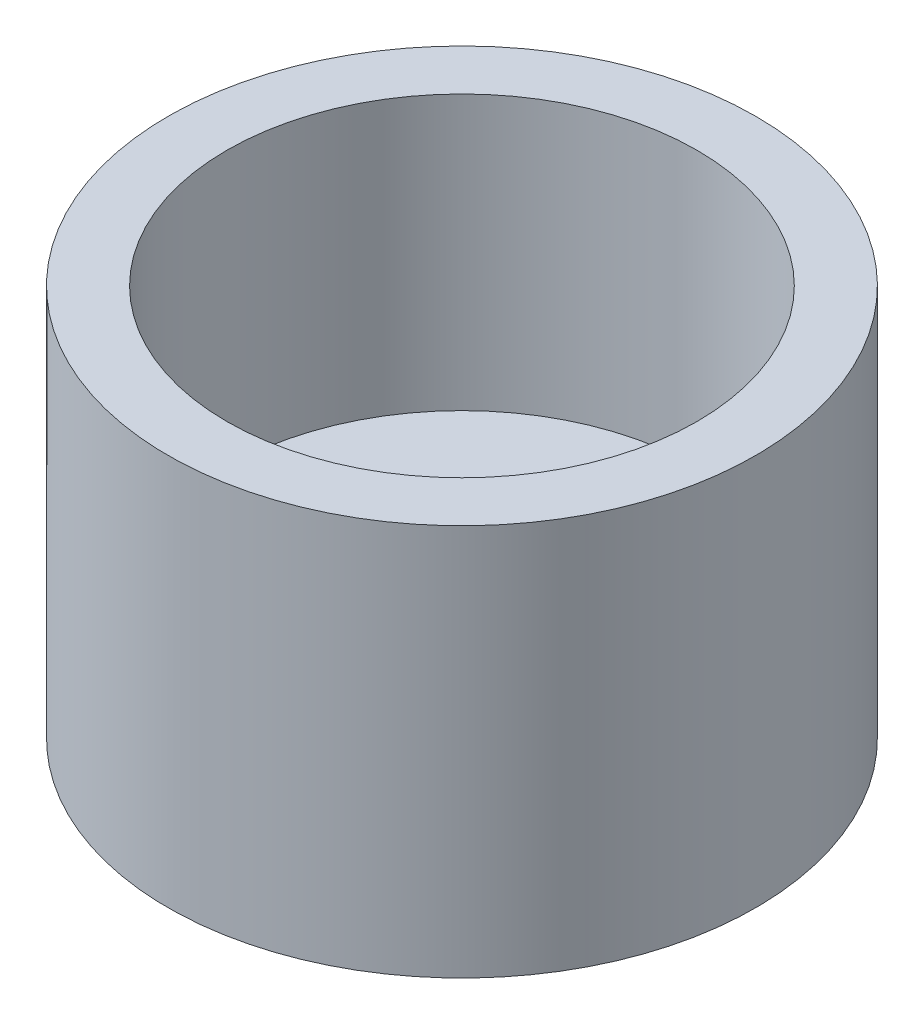
SolidWorks part; units mm, degrees
material "1.0035 (S185)"
ref_plane "Piano frontale" through (0, 0, 0) normal (0, 0, 1) x (1, 0, 0)
ref_plane "Piano superiore" through (0, 0, 0) normal (0, 1, 0) x (1, 0, 0)
ref_plane "Piano destro" through (0, 0, 0) normal (1, 0, 0) x (0, 0, -1)
sketch "Schizzo1" plane through (0, 0, 0) normal (0, 0, 1) x (1, 0, 0)
  line L0 (0, 0) -> (-15, 0)
  line L1 (-15, 0) -> (-15, 20)
  line L2 (-15, 20) -> (-12, 20)
  line L3 (-12, 20) -> (-12, 6)
  line L4 (-12, 6) -> (0, 6)
  line L5 (0, 6) -> (0, 0)
  line L6 (0, 0) -> (0, 10.8439) construction
  dimension "D1" = 30
  dimension "D2" = 24
  dimension "D3" = 6
  dimension "D4" = 20
revolve "Rivoluzione1" add sketch "Schizzo1" angle 360 about L6
sketch "Schizzo2" plane through (0, 0, 0) normal (0, -1, 0) x (1, 0, 0)
  circle A0 centre (0, 0) radius 1.585
  dimension "D1" = 3.17
extrude "Taglio-Estrusione1" cut sketch "Schizzo2" against normal blind 10
sketch "Schizzo3" plane through (0, 0, 0) normal (0, -1, 0) x (1, 0, 0)
  circle A0 centre (0, 0) radius 1.019
  circle A1 centre (0, 0) radius 1.5875
  dimension "D1" = 3.175
extrude "Estrusione-Estrusione1" [suppressed] add sketch "Schizzo3" along normal blind 8
sketch "Schizzo4" plane through (0, 0, 0) normal (0, 0, 1) x (1, 0, 0)
  line L0 (0, 0) -> (0, -9.8437)
